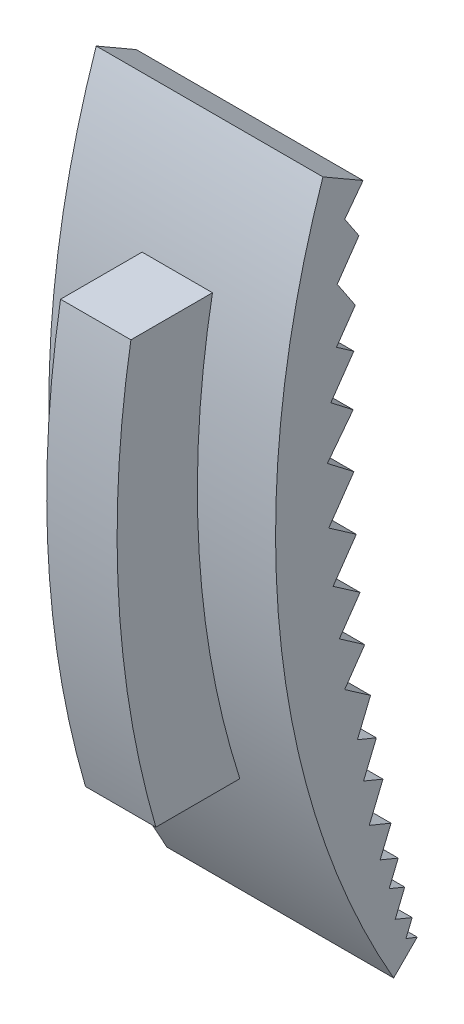
SolidWorks part; units mm, degrees
material "ABS"
ref_plane "Front Plane" through (0, 0, 0) normal (0, 0, 1) x (1, 0, 0)
ref_plane "Top Plane" through (0, 0, 0) normal (0, 1, 0) x (1, 0, 0)
ref_plane "Right Plane" through (0, 0, 0) normal (1, 0, 0) x (0, 0, -1)
sketch "Sketch1" plane through (0, 0, 0) normal (1, 0, 0) x (0, 0, -1)
  line L0 (13.97, 5.7716) -> (12.7, 4.5016)
  line L1 (12.7, 4.5016) -> (13.97, 4.5016) construction
  line L2 (13.97, 4.5016) -> (13.97, 5.7716) construction
  line L3 (0, 0) -> (12.7, 0) construction
  line L4 (12.7, 0) -> (12.7, 4.5016) construction
  line L5 (7.161, 37.084) -> (2.7748, 37.084)
  line L6 (8.6325, 13.716) -> (4.1172, 13.716)
  arc A0 (8.9448, 43.8527) -> (12.7, 4.5016) centre (54.1734, 28.3141) ccw
  arc A1 (12.4317, 51.6531) -> (8.9448, 43.8527) centre (54.1734, 28.3141) ccw
  arc A2 (12.4317, 51.6531) -> (13.97, 5.7716) centre (112.1185, 32.0287) ccw
  arc A3 (2.7748, 37.084) -> (4.1172, 13.716) centre (54.1734, 28.3141) ccw
  dimension "D3" = 101.6
  dimension "D1" = 1.27
  dimension "D2" = 45
  dimension "D4" = 37.084
  dimension "D5" = 13.716
extrude "Yükseklik-Ekstrüzyon1" add sketch "Sketch1" along normal mid plane 3.7846 contours A2 A1 A0 L0 | L5 A3 L6 A0 region at (0, 26.2135, -9.5328) region at (0, 25.3444, -4.7454)
extrude "Yükseklik-Ekstrüzyon2" add sketch "Sketch1<3>" along normal mid plane 12.192 contours A2 A1 A0 L0 region at (0, 26.2135, -9.5328)
sketch "Sketch1<3>" plane through (0, 0, 0) normal (1, 0, 0) x (0, 0, -1) same geometry as "Sketch1"
sketch "Çizim1" plane through (6.096, 0, 0) normal (1, 0, 0) x (0, 0, -1)
  line L0 (7.62, 44.45) -> (15.24, 40.0506)
  line L1 (7.62, 44.45) -> (7.62, 52.7506)
  line L2 (7.62, 52.7506) -> (15.24, 52.7506)
  line L3 (15.24, 52.7506) -> (15.24, 40.0506)
  line L4 (7.62, 44.45) -> (0, 44.45) construction
  line L5 (0, 44.45) -> (0, 0) construction
  point P7 (0, 0)
  dimension "D1" = 120
  dimension "D2" = 7.62
  dimension "D3" = 44.45
  dimension "D4" = 12.7
  dimension "D5" = 7.62
extrude "Kes-Ekstrüzyon1" cut sketch "Çizim1" against normal blind 12.192 contours L1 L2 L3 L0
sketch "Çizim2" plane through (6.096, 0, 0) normal (1, 0, 0) x (0, 0, -1)
  line L0 (11.056, 42.4662) -> (10.0705, 41.1538)
  line L1 (10.0705, 41.1538) -> (10.8337, 40.0073)
  line L2 (10.8337, 40.0073) -> (9.6663, 38.3268)
  line L3 (9.6663, 38.3268) -> (10.6369, 36.8689)
  line L4 (10.6369, 36.8689) -> (9.6257, 35.4132)
  line L5 (9.6257, 35.4132) -> (10.5593, 34.7647)
  line L6 (10.5593, 34.7647) -> (9.3198, 32.9804)
  line L7 (9.3198, 32.9804) -> (10.5233, 32.0575)
  line L8 (10.5233, 32.0575) -> (9.1355, 30.2477)
  line L9 (9.1355, 30.2477) -> (10.5647, 29.1518)
  line L10 (10.5647, 29.1518) -> (9.2104, 27.2021)
  line L11 (9.2104, 27.2021) -> (10.6933, 26.1719)
  line L12 (10.6933, 26.1719) -> (9.443, 24.372)
  line L13 (9.443, 24.372) -> (10.8947, 23.3635)
  line L14 (10.8947, 23.3635) -> (9.7786, 21.7569)
  line L15 (9.7786, 21.7569) -> (11.1459, 20.8071)
  line L16 (11.1459, 20.8071) -> (10.066, 19.2525)
  line L17 (10.066, 19.2525) -> (11.4577, 18.2857)
  line L18 (11.4577, 18.2857) -> (10.7522, 16.5738)
  line L19 (10.7522, 16.5738) -> (11.7713, 16.1539)
  line L20 (11.7713, 16.1539) -> (11.0827, 14.4829)
  line L21 (11.0827, 14.4829) -> (12.1256, 14.0531)
  line L22 (12.1256, 14.0531) -> (11.3891, 12.266)
  line L23 (11.3891, 12.266) -> (12.5593, 11.7837)
  line L24 (12.5593, 11.7837) -> (11.9743, 10.3642)
  line L25 (11.9743, 10.3642) -> (12.9459, 9.9638)
  line L26 (12.9459, 9.9638) -> (12.4593, 8.783)
  line L27 (12.4593, 8.783) -> (13.297, 8.4378)
  line L28 (13.297, 8.4378) -> (12.7844, 7.1941)
  line L29 (12.7844, 7.1941) -> (13.6967, 6.8182)
  line L30 (13.6967, 6.8182) -> (13.3622, 6.0065)
  line L31 (13.3622, 6.0065) -> (13.97, 5.7716)
  line L32 (11.056, 42.4662) -> (16.6412, 42.4662)
  line L33 (16.6412, 42.4662) -> (16.6412, 5.7716)
  line L34 (16.6412, 5.7716) -> (13.97, 5.7716)
  line L35 (13.97, 5.7716) -> (12.7, 4.5016) construction
  arc A1 (11.056, 42.4662) -> (13.97, 5.7716) centre (112.4807, 32.0575) ccw construction
  arc A2 (11.056, 42.4662) -> (13.97, 5.7716) centre (112.1185, 32.0287) ccw construction
  point P27 (11.056, 42.4662)
  point P38 (13.97, 5.7716)
extrude "Kes-Ekstrüzyon2" cut sketch "Çizim2" against normal blind 12.192
